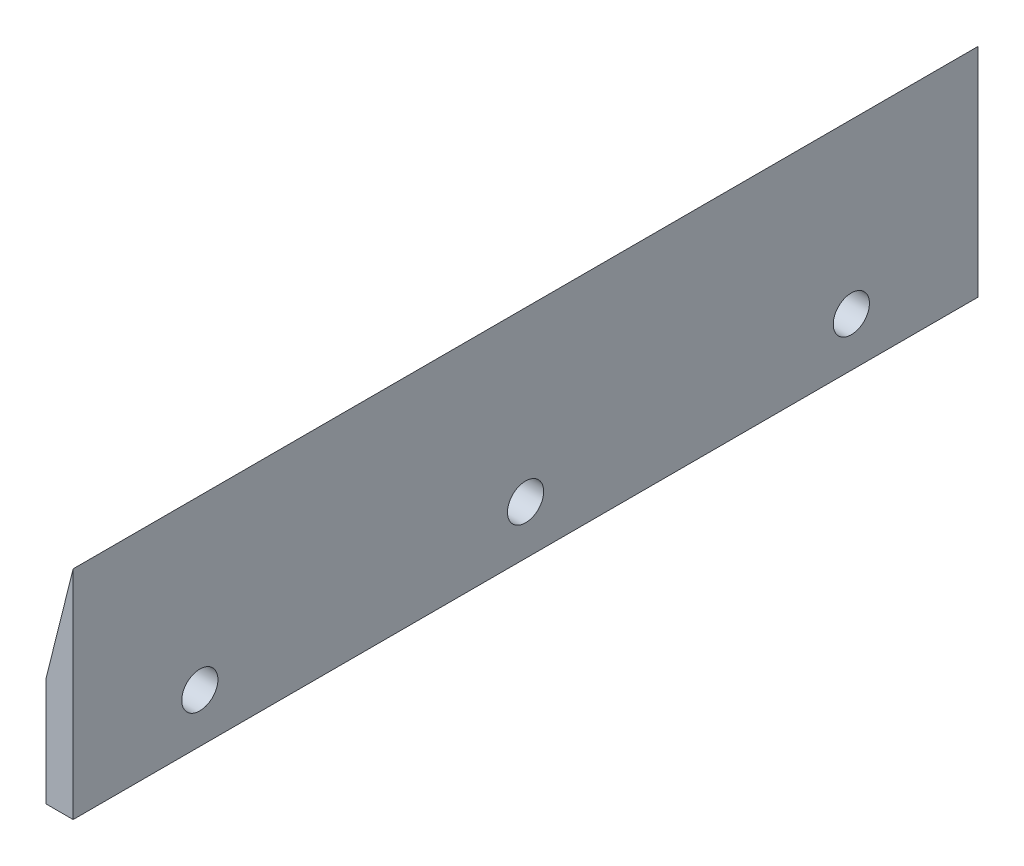
SolidWorks part; units mm, degrees
ref_plane "前基準面" through (0, 0, 0) normal (0, 0, 1) x (1, 0, 0)
ref_plane "上基準面" through (0, 0, 0) normal (0, 1, 0) x (1, 0, 0)
ref_plane "右基準面" through (0, 0, 0) normal (1, 0, 0) x (0, 0, -1)
sketch "草圖1" plane through (0, 0, 0) normal (0, 0, 1) x (1, 0, 0)
  line L0 (-5.0196, 177.5472) -> (-12.5196, 177.5472)
  line L1 (-12.5196, 177.5472) -> (-12.5196, 207.5472)
  line L2 (-12.5196, 207.5472) -> (-5.0196, 237.5472)
  line L3 (-5.0196, 237.5472) -> (-5.0196, 177.5472)
  dimension "D1" = 60
  dimension "D2" = 30
extrude "填料-伸長1" add sketch "草圖1" along normal blind 250
ref_plane "平面1" through (-12.5196, 0, 0) normal (1, 0, 0) x (0, 0, -1)
sketch "草圖2" plane through (-12.5196, 0, 0) normal (1, 0, 0) x (0, 0, -1)
  line L1 (0, 207.5472) -> (0, 177.5472) construction
  circle A0 centre (-215, 191.067) radius 5
  circle A1 centre (-125, 191.067) radius 5
  circle A2 centre (-35, 191.067) radius 5
  dimension "D1" = 10
  dimension "D2" = 10
  dimension "D3" = 10
  dimension "D4" = 90
  dimension "D5" = 90
  dimension "D6" = 35
extrude "除料-伸長1" cut sketch "草圖2" along normal through all
